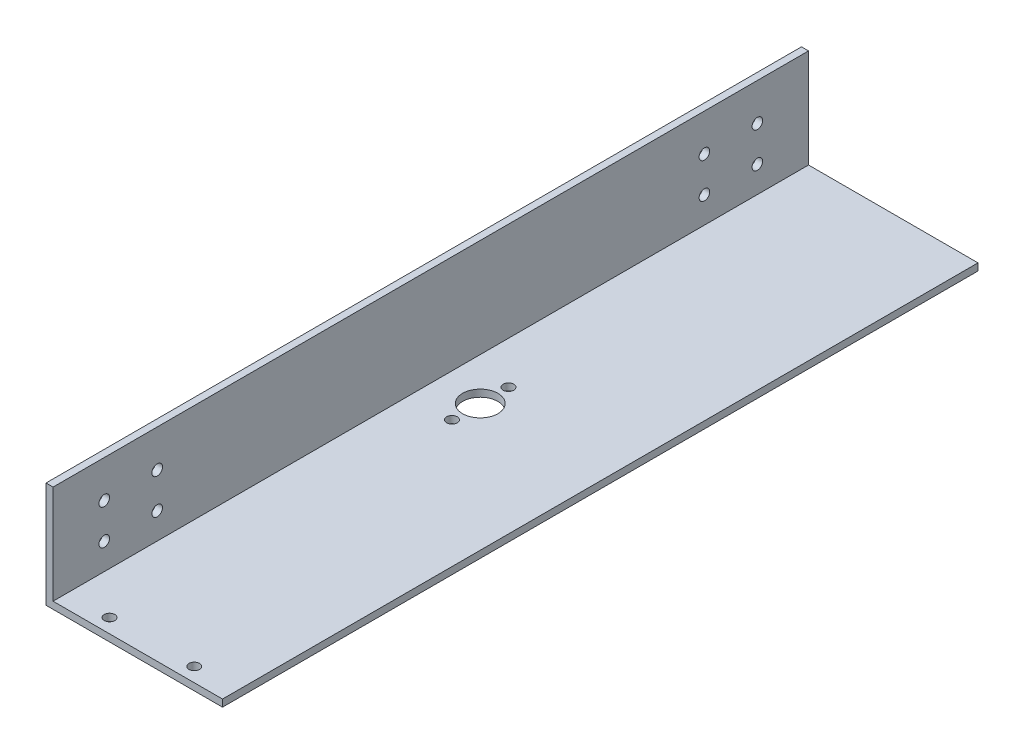
SolidWorks part; units mm, degrees
ref_plane "Front Plane" through (0, 0, 0) normal (0, 0, 1) x (1, 0, 0)
ref_plane "Top Plane" through (0, 0, 0) normal (0, 1, 0) x (1, 0, 0)
ref_plane "Right Plane" through (0, 0, 0) normal (1, 0, 0) x (0, 0, -1)
sketch "Sketch1" plane through (0, 0, 0) normal (0, 0, 1) x (1, 0, 0)
  line L0 (0, 0) -> (0, 30)
  line L1 (0, 30) -> (2, 30)
  line L2 (2, 30) -> (2, 2)
  line L3 (2, 2) -> (50, 2)
  line L4 (50, 2) -> (50, 0)
  line L5 (50, 0) -> (0, 0)
extrude "Boss-Extrude1" add sketch "Sketch1" along normal up to surface (214 mm away)
sketch "Sketch2" plane through (0, 0, 0) normal (0, -1, 0) x (1, 0, 0)
  circle A0 centre (14, 105) radius 5
extrude "Cut-Extrude1" cut sketch "Sketch2" against normal through all
sketch "Sketch4" plane through (0, 0, 0) normal (0, -1, 0) x (-1, 0, 0)
  circle A0 centre (-14, -113) radius 1.5
  circle A1 centre (-14, -97) radius 1.5
extrude "Cut-Extrude3" cut sketch "Sketch4" against normal through all
sketch "Sketch6" plane through (2, 0, 0) normal (1, 0, 0) x (0, 0, -1)
  circle A0 centre (-199.5, 9.45) radius 1.5
  circle A1 centre (-199.5, 19.45) radius 1.5
  circle A2 centre (-184.5, 9.45) radius 1.5
  circle A3 centre (-184.5, 19.45) radius 1.5
hole_wizard "Ø3.0 (3) Diameter Hole1" positions "Sketch7" profile "Sketch8" hole size "Ø3.0" standard "ISO" end condition through all
sketch "Sketch7" plane through (2, 0, 0) normal (1, 0, 0) x (0, 0, -1)
  point P0 (-199.5, 9.45)
  point P3 (-199.5, 19.45)
  point P6 (-184.5, 19.45)
  point P9 (-184.5, 9.45)
  point P12 (-29.5, 19.45)
  point P15 (-29.5, 9.45)
  point P18 (-14.5, 9.45)
  point P21 (-14.5, 19.45)
sketch "Sketch8" plane through (2, 9.45, 199.5) normal (0, 1, 0) x (0, 0, -1)
  line L0 (0, 0) -> (0, 2)
  line L1 (0, 2) -> (1.5, 2)
  line L2 (1.5, 2) -> (1.5, 0)
  line L5 (1.5, 0) -> (0, 0)
  line L11 (0, -6.35) -> (0, 107.95) construction
  dimension "Thru Hole Dia." = 3
  dimension "Thru Hole Depth" = 2
hole_wizard "Ø3.0 (3) Diameter Hole2" positions "Sketch11" profile "Sketch12" hole size "Ø3.0" standard "ISO" end condition through all
sketch "Sketch11" plane through (-23.4076, 2, 151.138) normal (0, 1, 0) x (0, 0, 1)
  point P0 (58.862, 61.4076)
  point P1 (58.862, 37.4076)
sketch "Sketch12" plane through (38, 2, 210) normal (1, 0, 0) x (0, 0, 1)
  line L0 (0, 0) -> (0, 2)
  line L1 (0, 2) -> (1.5, 2)
  line L2 (1.5, 2) -> (1.5, 0)
  line L5 (1.5, 0) -> (0, 0)
  line L11 (0, -6.35) -> (0, 107.95) construction
  dimension "Thru Hole Dia." = 3
  dimension "Thru Hole Depth" = 2
